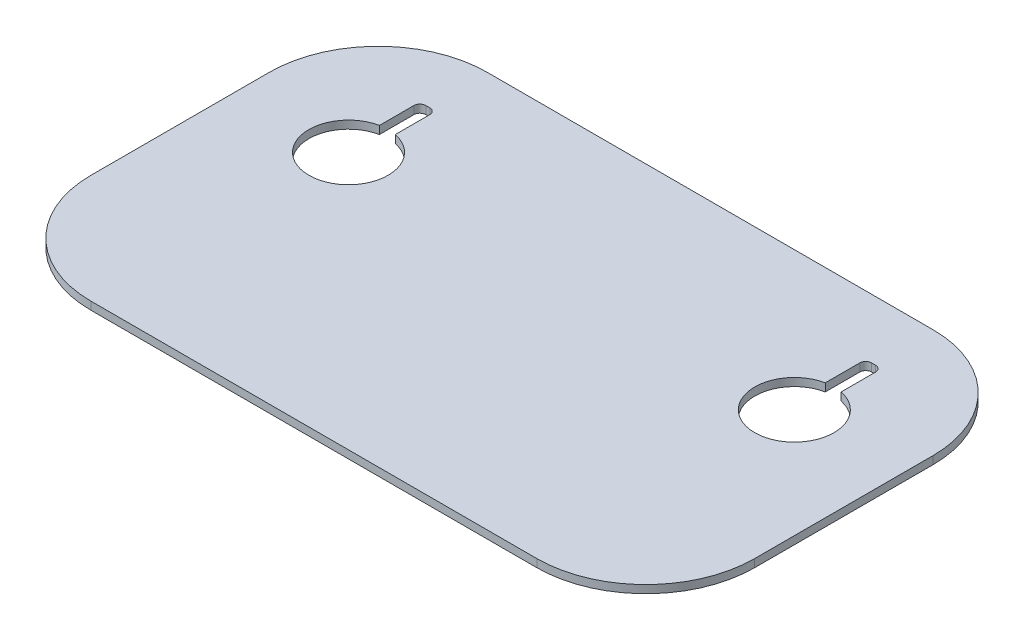
SolidWorks part; units mm, degrees
ref_plane "Front Plane" through (0, 0, 0) normal (0, 0, 1) x (1, 0, 0)
ref_plane "Top Plane" through (0, 0, 0) normal (0, 1, 0) x (1, 0, 0)
ref_plane "Right Plane" through (0, 0, 0) normal (1, 0, 0) x (0, 0, -1)
sketch "Sketch1" plane through (0, 0, 0) normal (0, 1, 0) x (1, 0, 0)
  line L1 (55, 0) -> (280, 0)
  line L2 (0, 55) -> (0, 145)
  line L3 (55, 200) -> (280, 200)
  line L4 (335, 55) -> (335, 145)
  arc A0 (55, 0) -> (0, 55) centre (55, 55) cw
  arc A1 (280, 0) -> (335, 55) centre (280, 55) ccw
  arc A2 (280, 200) -> (335, 145) centre (280, 145) cw
  arc A3 (0, 145) -> (55, 200) centre (55, 145) cw
  point P7 (0, 0)
  point P12 (335, 200)
  point P15 (0, 200)
  dimension "D3" = 55
  dimension "D1" = 335
  dimension "D2" = 200
extrude "Boss-Extrude1" add sketch "Sketch1" along normal blind 4
sketch "Sketch3" plane through (0, 4, 0) normal (0, 1, 0) x (1, 0, 0)
  line L0 (55, 200) -> (55, 0) construction
  line L1 (280, 200) -> (280, 0) construction
  line L2 (0, 130) -> (335, 130) construction
  line L3 (280, 200) -> (55, 200) construction
  line L4 (55, 0) -> (280, 0) construction
  line L5 (0, 145) -> (0, 55) construction
  line L6 (335, 55) -> (335, 145) construction
  line L7 (51, 167) -> (51, 149.5959)
  line L8 (167.5, 200) -> (167.5, 0) construction
  line L9 (59, 167) -> (59, 149.5959)
  line L10 (54, 170) -> (56, 170)
  line L11 (284, 167) -> (284, 149.5959)
  line L12 (281, 170) -> (279, 170)
  line L13 (276, 167) -> (276, 149.5959)
  arc A0 (59, 149.5959) -> (51, 149.5959) centre (55, 130) cw
  arc A1 (56, 170) -> (59, 167) centre (56, 167) cw
  arc A2 (51, 167) -> (54, 170) centre (54, 167) cw
  arc A3 (276, 149.5959) -> (284, 149.5959) centre (280, 130) ccw
  arc A4 (279, 170) -> (276, 167) centre (279, 167) ccw
  arc A5 (284, 167) -> (281, 170) centre (281, 167) ccw
  point P21 (59, 170)
  point P26 (51, 170)
  dimension "D4" = 40
  dimension "D6" = 20
  dimension "D7" = 3
  dimension "D1" = 70
  dimension "D2" = 55
  dimension "D3" = 55
  dimension "D5" = 8
extrude "Cut-Extrude1" cut sketch "Sketch3" against normal through all
